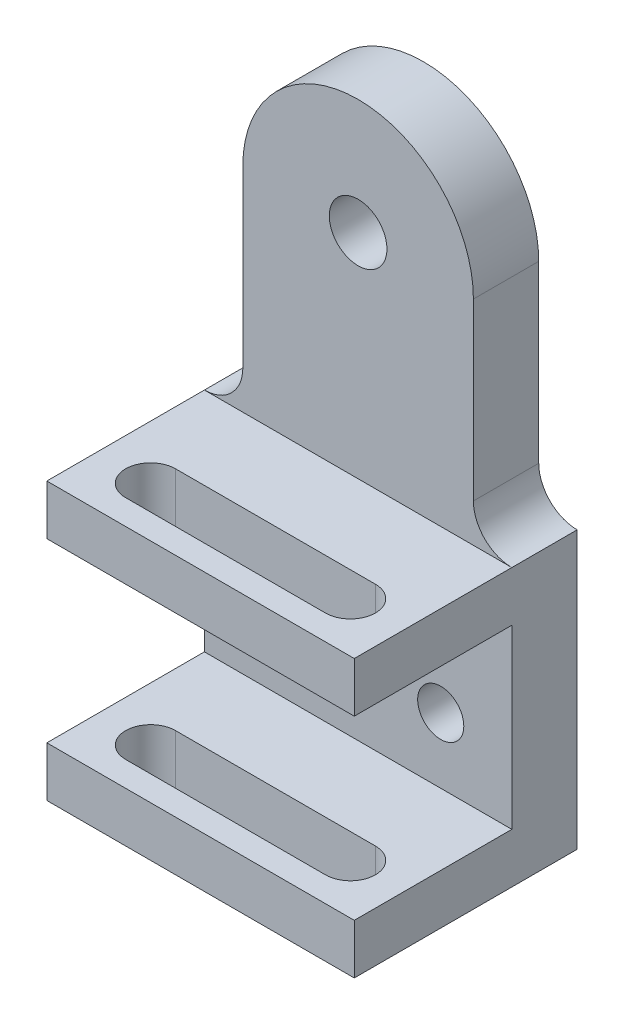
SolidWorks part; units mm, degrees
ref_plane "Front Plane" through (0, 0, 0) normal (0, 0, 1) x (1, 0, 0)
ref_plane "Top Plane" through (0, 0, 0) normal (0, 1, 0) x (1, 0, 0)
ref_plane "Right Plane" through (0, 0, 0) normal (1, 0, 0) x (0, 0, -1)
sketch "Sketch1" plane through (0, 0, 0) normal (0, 1, 0) x (1, 0, 0)
  line L1 (-40, 29) -> (40, 29)
  line L2 (-40, 29) -> (-40, -29)
  line L3 (-40, -29) -> (40, -29)
  line L4 (40, 29) -> (40, -29)
  line L5 (-40, 29) -> (40, -29) construction
  line L6 (-40, -29) -> (40, 29) construction
  point P0 (0, 0)
  dimension "D1" = 80
  dimension "D2" = 58
extrude "Boss-Extrude1" add sketch "Sketch1" along normal blind 13
sketch "Sketch2" plane through (0, 13, 0) normal (0, 1, 0) x (1, 0, 0)
  line L0 (40, -29) -> (40, 29) construction
  line L1 (-40, 29) -> (40, 29)
  line L2 (-40, 29) -> (-40, 12)
  line L3 (-40, 12) -> (40, 12)
  line L4 (40, 29) -> (40, 12)
  dimension "D1" = 17
extrude "Boss-Extrude2" add sketch "Sketch2" along normal blind 59 contours L3 L4 L1 L2
sketch "Sketch3" plane through (0, 0, -12) normal (0, 0, 1) x (1, 0, 0)
  line L0 (40, 72) -> (40, 13) construction
  line L1 (-40, 72) -> (40, 72)
  line L2 (-40, 72) -> (-40, 59)
  line L3 (-40, 59) -> (40, 59)
  line L4 (40, 72) -> (40, 59)
  dimension "D1" = 13
extrude "Boss-Extrude3" add sketch "Sketch3" along normal blind 41 contours L1 L4 L3 L2
sketch "Sketch4" plane through (0, 72, 0) normal (0, 1, 0) x (1, 0, 0)
  line L0 (40, 29) -> (40, -29) construction
  line L1 (-40, 29) -> (40, 29)
  line L2 (-40, 29) -> (-40, 12)
  line L3 (-40, 12) -> (40, 12)
  line L4 (40, 29) -> (40, 12)
  dimension "D1" = 17
extrude "Boss-Extrude4" add sketch "Sketch4" along normal blind 55.5 contours L3 L4 L1 L2
sketch "Sketch5" plane through (0, 0, -12) normal (0, 0, 1) x (1, 0, 0)
  line L0 (-40, 127.5) -> (40, 127.5) construction
  line L1 (-30, 127.5) -> (-30, 72)
  line L2 (-40, 72) -> (40, 72) construction
  line L3 (-30, 72) -> (-40, 72)
  line L4 (-40, 72) -> (-40, 127.5)
  line L5 (-40, 127.5) -> (-30, 127.5)
  circle A0 centre (0, 127.5) radius 30
  dimension "D1" = 60
extrude "Cut-Extrude1" cut sketch "Sketch5" against normal blind 55.5 contours L4 L5 L1 L3
sketch "Sketch7" plane through (0, 0, -12) normal (0, 0, 1) x (1, 0, 0)
  line L0 (-40, 72) -> (-30, 72)
  line L1 (40, 72) -> (30, 72)
  line L2 (-40, 72) -> (40, 72) construction
  line L3 (30, 72) -> (30, 127.5)
  line L4 (-30, 127.5) -> (40, 127.5) construction
  line L5 (30, 127.5) -> (40, 127.5)
  line L6 (40, 127.5) -> (40, 72) construction
  line L7 (40, 127.5) -> (40, 72)
  dimension "D1" = 10
extrude "Cut-Extrude2" cut sketch "Sketch7" against normal blind 55.5 contours L3 L5 L7 L1
sketch "Sketch8" plane through (0, 0, -12) normal (0, 0, 1) x (1, 0, 0)
  line L0 (-30, 127.5) -> (30, 127.5) construction
  circle A0 centre (0, 127.5) radius 30
extrude "Boss-Extrude5" add sketch "Sketch8" against normal blind 17 contours A0
sketch "Sketch9" plane through (0, 0, -12) normal (0, 0, 1) x (1, 0, 0)
  circle A0 centre (0, 127.5) radius 7.5
  dimension "D1" = 15
extrude "Cut-Extrude3" cut sketch "Sketch9" against normal blind 17 contours A0
fillet "Fillet1" radius 10 1 edges at (-30, 72, -20.5) type face fillet first side face at (-30, 99.75, -20.5) second side face at (0, 72, -10.25)
fillet "Fillet2" radius 10 1 edges at (30, 72, -20.5) type face fillet first side face at (30, 99.75, -20.5) second side face at (10, 72, -4)
sketch "Sketch10" plane through (0, 13, 0) normal (0, 1, 0) x (1, 0, 0)
  line L4 (-26, -9.5) -> (26, -9.5)
  line L6 (-26, -22.5) -> (26, -22.5)
  line L8 (-40, 12) -> (-40, -29) construction
  line L9 (-40, 12) -> (40, 12) construction
  arc A0 (-26, -9.5) -> (-26, -22.5) centre (-26, -16) ccw
  arc A1 (26, -22.5) -> (26, -9.5) centre (26, -16) ccw
  dimension "D1" = 6.5
  dimension "D2" = 14
  dimension "D3" = 66
  dimension "D4" = 28
extrude "Cut-Extrude4" cut sketch "Sketch10" against normal blind 17 contours L6 A1 L4 A0
sketch "Sketch11" plane through (0, 72, 0) normal (0, 1, 0) x (1, 0, 0)
  line L0 (0, -29) -> (26, -29)
  line L1 (-40, -29) -> (40, -29) construction
  line L4 (-26, -9.5) -> (26, -9.5)
  line L6 (-26, -22.5) -> (26, -22.5)
  line L7 (40, 12) -> (40, -29) construction
  line L8 (-40, 12) -> (40, 12) construction
  arc A0 (-26, -9.5) -> (-26, -22.5) centre (-26, -16) ccw
  arc A1 (26, -22.5) -> (26, -9.5) centre (26, -16) ccw
  dimension "D1" = 6.5
  dimension "D2" = 14
  dimension "D3" = 66
  dimension "D4" = 28
extrude "Cut-Extrude5" cut sketch "Sketch11" against normal blind 17 contours L6 A1 L4 A0
sketch "Sketch12" plane through (0, 0, -12) normal (0, 0, 1) x (1, 0, 0)
  line L0 (-40, 59) -> (-40, 13) construction
  circle A0 centre (-21.5, 30) radius 6
  circle A1 centre (21.5, 30) radius 6
  point P0 (20.2521, 30)
  point P8 (0, 0)
  dimension "D4" = 12
  dimension "D5" = 12
  dimension "D2" = 18.5
  dimension "D1" = 17
  dimension "D3" = 61.5
extrude "Cut-Extrude6" cut sketch "Sketch12" against normal blind 17 contours A0
sketch "Sketch13" plane through (0, 0, -12) normal (0, 0, 1) x (1, 0, 0)
  line L0 (-40, 59) -> (-40, 13) construction
  line L2 (-40, 59) -> (40, 59) construction
  circle A0 centre (21.5, 30) radius 6
  dimension "D2" = 12
  dimension "D1" = 61.5
  dimension "D3" = 29
extrude "Cut-Extrude7" cut sketch "Sketch13" against normal blind 17 contours A0
